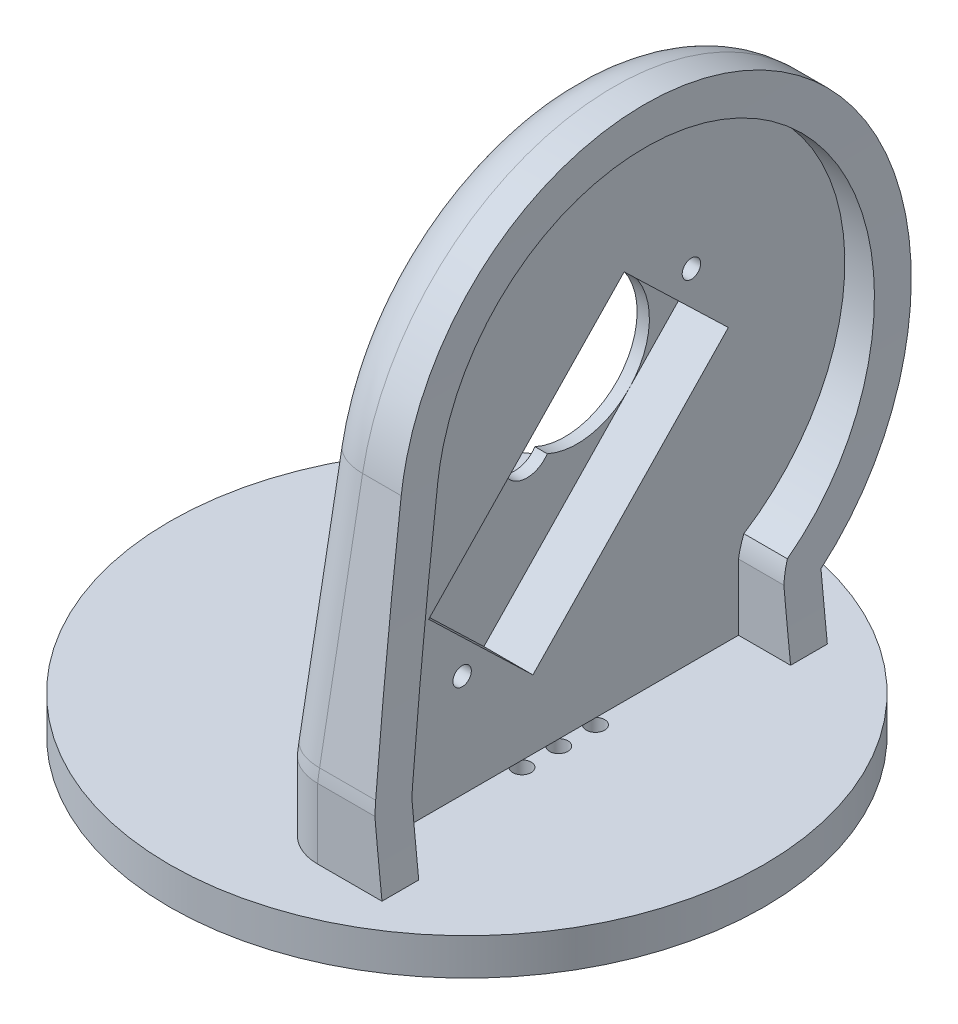
SolidWorks part; units mm, degrees
ref_plane "Front Plane" through (0, 0, 0) normal (0, 0, 1) x (1, 0, 0)
ref_plane "Top Plane" through (0, 0, 0) normal (0, 1, 0) x (1, 0, 0)
ref_plane "Right Plane" through (0, 0, 0) normal (1, 0, 0) x (0, 0, -1)
sketch "Sketch2" plane through (0, 0, 0) normal (0, 1, 0) x (1, 0, 0)
  line L0 (0, -7.5) -> (0, 7.5) construction
  line L1 (-7.5, 0) -> (7.5, 0) construction
  line L2 (-7.5, 7.5) -> (7.5, 7.5) construction
  line L3 (-7.5, 7.5) -> (-7.5, -7.5) construction
  line L4 (-7.5, -7.5) -> (7.5, -7.5) construction
  line L5 (7.5, 7.5) -> (7.5, -7.5) construction
  line L6 (-7.5, 7.5) -> (7.5, -7.5) construction
  line L7 (-7.5, -7.5) -> (7.5, 7.5) construction
  circle A0 centre (0, 0) radius 24.25
  circle A1 centre (0, 7.5) radius 0.75
  circle A3 centre (0, 0) radius 4
  circle A4 centre (-3, 7.5) radius 0.75
  circle A5 centre (3, 7.5) radius 0.75
  circle A6 centre (3, -7.5) radius 0.75
  circle A7 centre (0, -7.5) radius 0.75
  circle A8 centre (-3, -7.5) radius 0.75
  circle A9 centre (7.5, 0) radius 0.75
  circle A10 centre (7.5, 3) radius 0.75
  circle A11 centre (7.5, -3) radius 0.75
  circle A12 centre (-7.5, -3) radius 0.75
  circle A13 centre (-7.5, 0) radius 0.75
  circle A14 centre (-7.5, 3) radius 0.75
  point P7 (0, 0)
  dimension "D2" = 48.5
  dimension "D3" = 1.5
  dimension "D4" = 8
  dimension "D7" = 1.5
  dimension "D8" = 1.5
  dimension "D10" = 3
  dimension "D9" = 3
  dimension "D11" = 1.5
  dimension "D12" = 1.5
  dimension "D13" = 1.5
  dimension "D1" = 15
  dimension "D5" = 15
  dimension "D6" = 15
  dimension "D14" = 3
  dimension "D15" = 3
extrude "Boss-Extrude1" add sketch "Sketch2" along normal blind 3
sketch "Sketch4" plane through (0, 0, 0) normal (1, 0, 0) x (0, 0, -1)
  line L0 (15.17, 3) -> (-15.17, 3)
  line L1 (-15.17, 3) -> (-15.17, 8.5)
  line L2 (24.25, 3) -> (-24.25, 3) construction
  line L3 (15.17, 3) -> (15.17, 8.39)
  line L4 (-15.0596, 9.1736) -> (-11.5536, 28.2296)
  line L5 (-15.17, 3) -> (6, 25) construction
  arc A0 (15.17, 8.39) -> (15.6075, 9.9583) centre (22.5702, 7.1707) cw
  arc A1 (15.6075, 9.9583) -> (-11.5536, 28.2296) centre (6, 25) ccw
  arc A2 (-15.17, 8.5) -> (-15.0596, 9.1736) centre (2.1515, 6.0069) cw
  circle A3 centre (6, 25) radius 5.9
  point P3 (0, 3)
  point P15 (-3.5883, 15.0358)
  point P18 (6, 25)
  dimension "D3" = 7.5
  dimension "D5" = 17.5
  dimension "D7" = 11.8
  dimension "D1" = 30.34
  dimension "D2" = 5.39
  dimension "D4" = 5.5
  dimension "D8" = 6
  dimension "D9" = 25
extrude "Boss-Extrude2" add sketch "Sketch4" along normal blind 5 from offset 2
sketch "Sketch9" plane through (7, 0, 0) normal (1, 0, 0) x (0, 0, -1)
  line L0 (16.67, 3) -> (16.67, 8.2604) construction
  line L1 (-13.0288, 28.501) -> (-16.5348, 9.445) construction
  line L2 (-16.67, 8.6052) -> (-16.67, 3) construction
  line L3 (-11.5536, 28.2296) -> (-15.0596, 9.1736)
  line L4 (-15.17, 8.5) -> (-15.17, 3)
  line L5 (-15.17, 3) -> (-3.559, 3)
  line L6 (15.17, 3) -> (15.17, 8.39)
  line L7 (-11.5536, 28.2296) -> (-15.0596, 9.1736)
  line L8 (-15.17, 8.5) -> (-15.17, 3)
  line L9 (-15.17, 3) -> (-3.559, 3)
  line L10 (15.17, 3) -> (15.17, 8.39)
  line L11 (-11.5536, 28.2296) -> (-15.0596, 9.1736)
  line L12 (18.17, 3) -> (18.17, 8.0726)
  line L13 (-14.504, 28.7725) -> (-18.0101, 9.7164)
  line L14 (-18.17, 8.7063) -> (-18.17, 3)
  line L15 (-18.17, 3) -> (-13.67, 3)
  line L16 (-3.559, 3) -> (18.17, 3)
  line L27 (-3.559, 3) -> (-2.441, 3)
  line L28 (-3.559, 3) -> (-2.441, 3)
  line L29 (-2.441, 3) -> (-0.559, 3)
  line L30 (-2.441, 3) -> (-0.559, 3)
  line L31 (-0.559, 3) -> (0.559, 3)
  line L32 (-0.559, 3) -> (0.559, 3)
  line L33 (0.559, 3) -> (2.441, 3)
  line L34 (0.559, 3) -> (2.441, 3)
  line L35 (2.441, 3) -> (3.559, 3)
  line L36 (2.441, 3) -> (3.559, 3)
  line L37 (3.559, 3) -> (15.17, 3)
  line L38 (3.559, 3) -> (15.17, 3)
  arc A0 (16.8495, 8.98) -> (16.67, 8.2604) centre (22.5702, 7.1707) ccw construction
  arc A1 (16.8495, 8.98) -> (-13.0288, 28.501) centre (6, 25) ccw construction
  arc A2 (-16.5348, 9.445) -> (-16.67, 8.6052) centre (2.1515, 6.0069) ccw construction
  arc A3 (15.6075, 9.9583) -> (15.17, 8.39) centre (22.5702, 7.1707) ccw
  arc A4 (15.6075, 9.9583) -> (-11.5536, 28.2296) centre (6, 25) ccw
  arc A5 (-15.0596, 9.1736) -> (-15.17, 8.5) centre (2.1515, 6.0069) ccw
  arc A6 (15.6075, 9.9583) -> (15.17, 8.39) centre (22.5702, 7.1707) ccw
  arc A7 (15.6075, 9.9583) -> (-11.5536, 28.2296) centre (6, 25) ccw
  arc A8 (-15.0596, 9.1736) -> (-15.17, 8.5) centre (2.1515, 6.0069) ccw
  arc A9 (18.17, 8.0726) -> (18.17, 8.0726) centre (18.17, 8.0726) ccw
  arc A10 (18.17, 8.0726) -> (-14.504, 28.7725) centre (6, 25) ccw
  arc A11 (-18.0101, 9.7164) -> (-18.17, 8.7063) centre (2.1515, 6.0069) ccw
  arc A12 (-12.5487, 22.8208) -> (-13.67, 3) centre (86.2379, 7.2902) ccw
  line M14 (-15.17, 8.5) -> (-15.17, 3)
  line M16 (15.17, 3) -> (15.17, 8.39)
  arc M17 (15.17, 8.39) -> (15.6075, 9.9583) centre (22.5702, 7.1707) cw
  arc M18 (15.6075, 9.9583) -> (-11.5536, 28.2296) centre (6, 25) ccw
  line M19 (-11.5536, 28.2296) -> (-15.0596, 9.1736)
  arc M20 (-15.0596, 9.1736) -> (-15.17, 8.5) centre (2.1515, 6.0069) ccw
  dimension "D6" = 100
  dimension "D5" = 1.5
  dimension "D1" = 0
  dimension "D2" = 1.5
  dimension "D3" = 1.5
  dimension "D4" = 1.5
extrude "Boss-Extrude3" add sketch "Sketch9" along normal blind 4.5 and the other way up to surface (5 mm away) contours L13 A11 L14 L15 L11 L16 L12 A9 A10 M14 M20 M19 M18 M17 M16 other way up to face at (2, 10.7755, -0.3204)
sketch "Sketch10" plane through (0, 0, 0) normal (0, 0, 1) x (1, 0, 0)
  line L0 (11.5, 45.8482) -> (8.5, 45.8482)
  line L1 (11.5, 45.8482) -> (2, 45.8482) construction
  line L2 (2, 3) -> (11.5, 3) construction
  line L3 (11.25, 3) -> (11.5, 3)
  line L4 (11.5, 3) -> (11.5, 45.8482)
  arc A0 (8.5, 45.8482) -> (11.25, 3) centre (508.3883, 56.4187) ccw
  dimension "D3" = 500
  dimension "D1" = 3
  dimension "D2" = 0.25
extrude "Cut-Extrude2" cut sketch "Sketch10" against normal through all both and the other way through all
fillet "Fillet3" radius 4 5 edges at (2, 9.2123, 18.0963) (2, 5.5363, -18.17) (2, 5.8531, 18.17) (2, 19.2444, 16.2571) (2, 42.6114, -17.1573)
sketch "Sketch11" plane through (7, 0, 0) normal (1, 0, 0) x (0, 0, -1)
  line L0 (-15.17, 3) -> (20.4558, 40.0225) construction
  line L1 (-1.6055, 8.5873) -> (-10.1082, 16.7692)
  line L2 (-1.6055, 8.5873) -> (14.3423, 25.1604)
  line L3 (-10.1082, 16.7692) -> (5.8396, 33.3423)
  line L4 (14.3423, 25.1604) -> (5.8396, 33.3423)
  arc A0 (18.17, 8.0726) -> (-14.504, 28.7725) centre (6, 25) ccw construction
  circle A1 centre (6, 25) radius 5.9 construction
  point P2 (10.091, 29.2514)
  dimension "D1" = 11.8
  dimension "D2" = 5.9
  dimension "D3" = 5.9
  dimension "D4" = 23
extrude "Cut-Extrude3" cut sketch "Sketch11" against normal blind 4
sketch "Sketch12" plane through (3, 0, 0) normal (1, 0, 0) x (0, 0, -1)
  circle A0 centre (1.909, 20.7486) radius 2
  arc A1 (1.7486, 29.091) -> (10.2514, 20.909) centre (6, 25) ccw construction
  dimension "D1" = 4
extrude "Cut-Extrude4" cut sketch "Sketch12" against normal blind 10
sketch "Sketch14" plane through (7, 0, 0) normal (1, 0, 0) x (0, 0, -1)
  line L1 (-2.1343, 25.0558) -> (6.3684, 16.8739) construction
  line L2 (-10.1082, 16.7692) -> (5.8396, 33.3423) construction
  line L3 (14.3423, 25.1604) -> (-1.6055, 8.5873) construction
  circle A0 centre (11.3275, 30.8233) radius 0.75
  circle A1 centre (-7.3801, 11.3823) radius 0.75
  dimension "D1" = 1.5
  dimension "D2" = 2
extrude "Cut-Extrude5" cut sketch "Sketch14" against normal blind 2.5
